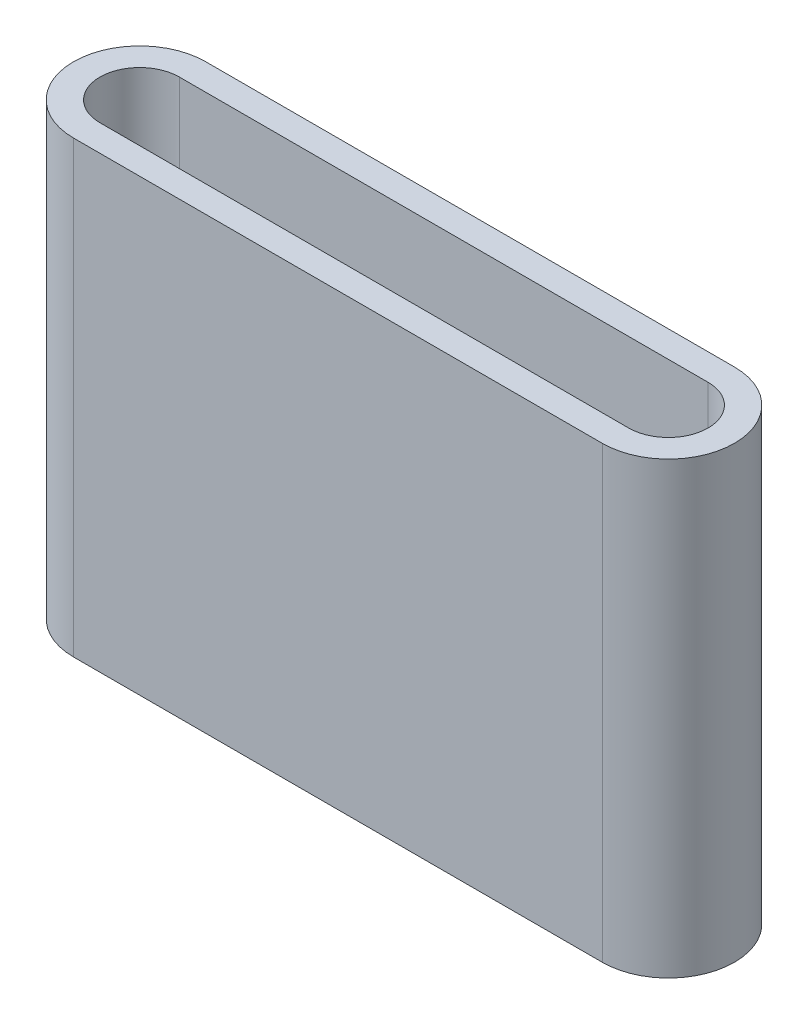
SolidWorks part; units mm, degrees
ref_plane "前视基准面" through (0, 0, 0) normal (0, 0, 1) x (1, 0, 0)
ref_plane "上视基准面" through (0, 0, 0) normal (0, 1, 0) x (1, 0, 0)
ref_plane "右视基准面" through (0, 0, 0) normal (1, 0, 0) x (0, 0, -1)
sketch "草图1" plane through (0, 0, 0) normal (0, 1, 0) x (1, 0, 0)
  line L0 (0, 0) -> (100, 0) construction
  line L1 (0, 12.5) -> (100, 12.5)
  line L2 (0, -12.5) -> (100, -12.5)
  arc A0 (0, 12.5) -> (0, -12.5) centre (0, 0) ccw
  arc A1 (100, -12.5) -> (100, 12.5) centre (100, 0) ccw
  point P3 (50, 0)
  dimension "D1" = 100
  dimension "D2" = 25
extrude "凸台-拉伸1" add sketch "草图1" along normal blind 20 and the other way blind 10
sketch "草图2" plane through (0, 20, 0) normal (0, 1, 0) x (1, 0, 0)
  line L2 (0, -12.5) -> (100, -12.5)
  line L3 (100, 12.5) -> (0, 12.5)
  line L4 (0, -12.5) -> (100, -12.5)
  line L5 (100, 12.5) -> (0, 12.5)
  arc A2 (0, 12.5) -> (0, -12.5) centre (0, 0) ccw
  arc A3 (100, -12.5) -> (100, 12.5) centre (100, 0) ccw
  arc A4 (0, 12.5) -> (0, -12.5) centre (0, 0) ccw
  arc A5 (100, -12.5) -> (100, 12.5) centre (100, 0) ccw
  dimension "D1" = 0
extrude "拉伸-薄壁1" add sketch "草图2" along normal blind 55 thin thin type one direction reverse wall 5
